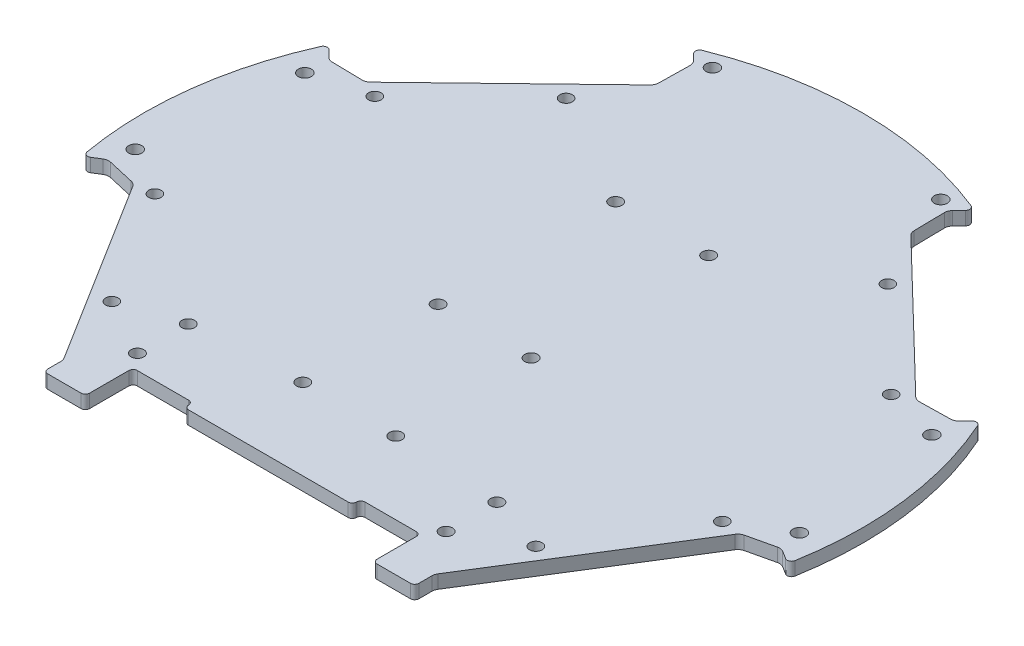
SolidWorks part; units mm, degrees
material "6061 Alloy"
ref_plane "Front Plane" through (0, 0, 0) normal (0, 0, 1) x (1, 0, 0)
ref_plane "Top Plane" through (0, 0, 0) normal (0, 1, 0) x (1, 0, 0)
ref_plane "Right Plane" through (0, 0, 0) normal (1, 0, 0) x (0, 0, -1)
sketch "Sketch1" plane through (0, 0, 0) normal (0, 1, 0) x (1, 0, 0)
  line L0 (0, 0) -> (0, -55.55) construction
  line L1 (-83.4462, -16.178) -> (-71.2857, -8.5793) construction
  line L6 (0, 0) -> (-59.046, 61.1439) construction
  line L7 (0, 0) -> (-72.0841, -45.0431) construction
  line L8 (-33.174, 78.2591) -> (-23.2129, 67.9442) construction
  line L9 (-72.0841, -45.0431) -> (-70.388, -43.9833) construction
  line L10 (-70.388, -43.9833) -> (-84.9608, -20.662) construction
  line L11 (-84.9608, -20.662) -> (-72.2401, -12.7132) construction
  line L12 (-72.2401, -12.7132) -> (-43.0945, -59.3558) construction
  line L13 (-43.0945, -59.3558) -> (-55.8152, -67.3046) construction
  line L14 (-55.8152, -67.3046) -> (-70.388, -43.9833) construction
  line L21 (-59.046, 61.1439) -> (-57.6566, 59.7052)
  line L22 (-77.4385, 40.6021) -> (-37.8748, 78.8083) construction
  line L23 (-73.9694, 32.6911) -> (-77.0537, 35.885)
  line L24 (-37.8748, 78.8083) -> (-27.4549, 68.0182) construction
  line L25 (-27.4549, 68.0182) -> (-67.0186, 29.812) construction
  line L26 (-67.0186, 29.812) -> (-77.4385, 40.6021) construction
  line L27 (-43.0945, -64.8266) -> (-34, -64.8266)
  line L33 (-86.5505, -18.1178) -> (-71.2857, -8.5793) construction
  line L34 (0, 0) -> (0, 50000) construction
  line L35 (0, 0) -> (-50000, 0) construction
  line L36 (-64.3366, -55.55) -> (-19.7189, -55.55) construction
  line L38 (-67.0927, 25.57) -> (-79.5965, 38.5181) construction
  line L39 (-54.9774, -64.8266) -> (0, -64.8266) construction
  line L40 (-35.7168, 80.8923) -> (-23.2129, 67.9442) construction
  line L41 (-38.9606, -60.3102) -> (-54.2255, -69.8488) construction
  line L42 (-34, -55.55) -> (-19.7189, -55.55) construction
  line L43 (-43.0945, -64.8266) -> (-43.0945, -58.4123) construction
  line L45 (73.9694, 32.6911) -> (77.0537, 35.885)
  line L46 (-71.2857, -8.5793) -> (-38.9606, -60.3102) construction
  line L47 (83.4462, -16.178) -> (79.6809, -13.8252)
  line L48 (69.4846, -16.1792) -> (43.8945, -57.132)
  line L50 (43.0945, -64.8266) -> (34, -64.8266)
  line L51 (34, -55.55) -> (34, -64.8266)
  line L52 (0, 0) -> (72.0841, -45.0431) construction
  line L53 (0, 0) -> (59.046, 61.1439) construction
  line L54 (-30.0897, 75.0653) -> (-30.2847, 63.8954)
  line L55 (-62.7996, 32.4961) -> (-30.2847, 63.8954)
  line L56 (-30.0897, 75.0653) -> (-33.174, 78.2591)
  line L57 (73.9694, 32.6911) -> (77.0537, 35.885)
  line L58 (30.0897, 75.0653) -> (33.174, 78.2591)
  line L59 (-34, -55.55) -> (-34, -53.55)
  line L60 (62.7996, 32.4961) -> (30.2847, 63.8954)
  line L61 (-73.9694, 32.6911) -> (-62.7996, 32.4961)
  line L62 (-77.0537, 35.885) -> (-67.0927, 25.57) construction
  line L63 (-83.4462, -16.178) -> (-79.6809, -13.8252)
  line L64 (-79.6809, -13.8252) -> (-69.4846, -16.1792)
  line L65 (-69.4846, -16.1792) -> (-43.8945, -57.132)
  line L66 (-27.4549, 68.0182) -> (-23.2129, 67.9442) construction
  line L67 (-72.2401, -12.7132) -> (-71.2857, -8.5793) construction
  line L68 (30.0897, 75.0653) -> (30.2847, 63.8954)
  line L69 (73.9694, 32.6911) -> (62.7996, 32.4961)
  line L70 (-34, -55.55) -> (-34, -64.8266)
  line L71 (79.6809, -13.8252) -> (69.4846, -16.1792)
  line L72 (-34, -53.55) -> (-20, -53.55)
  line L73 (-20, -53.55) -> (-19.7189, -55.55)
  line L74 (-19.7189, -55.55) -> (19.7189, -55.55)
  line L75 (20, -53.55) -> (19.7189, -55.55)
  line L76 (34, -53.55) -> (20, -53.55)
  line L77 (34, -55.55) -> (34, -53.55)
  line L78 (-43.0945, -64.8266) -> (-43.8945, -64.8266)
  line L79 (-19.7189, -55.55) -> (0, -55.55) construction
  line L80 (-19.7189, -55.55) -> (34, -55.55) construction
  line L81 (-43.8945, -64.8266) -> (-43.8945, -57.132)
  line L82 (-43.0945, -58.4123) -> (-43.8945, -57.132) construction
  line L83 (43.8945, -64.8266) -> (43.8945, -57.132)
  line L84 (43.0945, -64.8266) -> (43.8945, -64.8266)
  line L97 (-23.2129, 67.9442) -> (-67.0927, 25.57) construction
  circle A0 centre (0, 0) radius 85 construction
  circle A1 centre (0, 0) radius 90 construction
  arc A51 (-77.0537, 35.885) -> (-83.4462, -16.178) centre (0, 0) ccw
  arc A52 (77.0537, 35.885) -> (83.4462, -16.178) centre (0, 0) cw
  arc A54 (-33.174, 78.2591) -> (33.174, 78.2591) centre (0, 0) cw
  point P29 (-31.6318, 76.6622)
  point P33 (-47.2368, 48.9151)
  point P34 (31.6318, 76.6622)
  point P35 (-57.6673, -36.0345)
  point P85 (-57.6566, 59.7052)
  dimension "D2" = 58
  dimension "D10" = 82
  dimension "D12" = 170
  dimension "D14" = 34
  dimension "D13" = 2
  dimension "D15" = 3
  dimension "D3" = 180
  dimension "D4" = 64.8266
  dimension "D5" = 44
  dimension "D6" = 15
  dimension "D7" = 55
  dimension "D8" = 55.55
  dimension "D9" = 2
  dimension "D11" = 2
  dimension "D16" = 7
  dimension "D17" = 7
  dimension "D18" = 0.5
  dimension "D19" = 1
  dimension "D20" = 14
  dimension "D21" = 0.8
extrude "Boss-Extrude4" add sketch "Sketch1" along normal mid plane 3.175 contours A0 L70 region at (0, 0, -7.394)
ref_point "Rear_Axle_Center (L)"
ref_axis "Rear_Axle_Proj (L)" through (46.5421, 0, -48.1958) along (0, 1, 0)
ref_point "Front_Axle_Center (L)"
ref_axis "Front_Axle_Proj (L)" through (57.2432, 0, 35.7696) along (0, 1, 0)
ref_point "Front_Axle_Center (R)"
ref_axis "Front_Axle_Proj (R)" through (-57.2432, 0, 35.7696) along (0, 1, 0)
ref_point "Read_Axle_Center (R)"
ref_axis "Rear_Axle_Proj (R)" through (-46.5421, 0, -48.1958) along (0, 1, 0)
sketch "Sketch17" plane through (0, 1.5875, 0) normal (0, 1, 0) x (1, 0, 0)
  line L0 (0, -50.55) -> (0, -55.55) construction
  line L1 (-19.7189, -55.55) -> (19.7189, -55.55) construction
  circle A0 centre (0, -50.55) radius 8.5
  dimension "D1" = 17
  dimension "D2" = 5
extrude "Boss-Extrude5" [suppressed] add sketch "Sketch17" against normal up to surface (3.175 mm away)
ref_plane "Plane1" through (0, 0, 10) normal (0, 0, 1) x (1, 0, 0)
hole_wizard "M3 Clearance Hole3" positions "Sketch18" profile "Sketch19" hole size "M3" standard "ANSI Metric" end condition through all
sketch "Sketch18" plane through (0, -1.5875, 0) normal (0, -1, 0) x (-1, 0, 0)
  line L0 (-36.5, -50) -> (-36.5, -38) construction
  line L3 (0, 0) -> (0, -38) construction
  line L4 (36.5, -50) -> (36.5, -38) construction
  line L6 (0, -38) -> (36.5, -38) construction
  line L8 (0, -38) -> (-36.5, -38) construction
  line L9 (-36.5, -44) -> (36.5, -44) construction
  line L10 (0, -44) -> (0, 0) construction
  point P1 (36.5, -50)
  point P3 (36.5, -38)
  point P5 (-36.5, -50)
  point P33 (-36.5, -38)
  dimension "D1" = 12
  dimension "D2" = 73
  dimension "D4" = 38
sketch "Sketch19" plane through (-36.5, -1.5875, 50) normal (1, 0, 0) x (0, 0, -1)
  line L0 (0, 0) -> (0, 3.175)
  line L1 (0, 3.175) -> (1.5, 3.175)
  line L2 (1.5, 3.175) -> (1.5, 0)
  line L5 (1.5, 0) -> (0, 0)
  line L11 (0, -6.35) -> (0, 107.95) construction
  dimension "Thru Hole Dia." = 3
  dimension "Thru Hole Depth" = 3.175
hole_wizard "M3 Clearance Hole1" positions "Sketch11" profile "Sketch12" hole size "M3" standard "ANSI Metric" end condition through all
sketch "Sketch11" plane through (0, 1.5875, 0) normal (0, 1, 0) x (1, 0, 0)
  line L0 (83.4462, -16.178) -> (79.6809, -13.8252) construction
  line L2 (73.9694, 32.6911) -> (77.0537, 35.885) construction
  line L4 (-73.9694, 32.6911) -> (-77.0537, 35.885) construction
  line L6 (0, 0) -> (0, -50000) construction
  line L7 (78.4111, 9.6277) -> (84.3664, 10.3589) construction
  line L10 (74.155, 27.2403) -> (78.5423, -8.4914) construction
  line L12 (78.4111, 9.6277) -> (76.3487, 9.3744) construction
  arc A7 (77.964, -12.7523) -> (72.563, 31.2347) centre (0, 0) ccw construction
  arc A13 (-77.964, -12.7523) -> (-72.563, 31.2347) centre (0, 0) cw construction
  arc A17 (83.4462, -16.178) -> (77.0537, 35.885) centre (0, 0) ccw construction
  point P34 (78.5423, -8.4914)
  point P66 (74.155, 27.2403)
  point P70 (-74.155, 27.2403)
  point P71 (-78.5423, -8.4914)
  dimension "D1" = 6
  dimension "D2" = 36
sketch "Sketch12" plane through (-78.5423, 1.5875, 8.4914) normal (1, 0, 0) x (0, 0, 1)
  line L0 (0, 0) -> (0, 3.175)
  line L1 (0, 3.175) -> (1.55, 3.175)
  line L2 (1.55, 3.175) -> (1.55, 0)
  line L5 (1.55, 0) -> (0, 0)
  line L11 (0, -6.35) -> (0, 107.95) construction
  dimension "Thru Hole Dia." = 3.1
  dimension "Thru Hole Depth" = 3.175
hole_wizard "M3 Clearance Hole4" positions "Sketch9" profile "Sketch10" hole size "M3" standard "ANSI Metric" end condition through all
sketch "Sketch9" plane through (0, -1.5875, 0) normal (0, -1, 0) x (-1, 0, 0)
  line L0 (0, 0) -> (0, 63.4318) construction
  line L1 (-38.0437, 52.9272) -> (38.0437, 52.9272) construction
  line L3 (61.0625, 30.6981) -> (-61.0625, 30.6981) construction
  line L4 (-67.0993, -15.2789) -> (67.0993, -15.2789) construction
  line L5 (50.1419, -42.4164) -> (-50.1419, -42.4164) construction
  line L6 (-61.0625, 30.6981) -> (-38.0437, 52.9272) construction
  line L7 (38.0437, 52.9272) -> (61.0625, 30.6981) construction
  line L8 (67.0993, -15.2789) -> (50.1419, -42.4164) construction
  line L9 (-50.1419, -42.4164) -> (-67.0993, -15.2789) construction
  line L10 (0, 0) -> (-44.8055, 46.3974) construction
  line L11 (0, 0) -> (44.8055, 46.3974) construction
  line L12 (0, 0) -> (-96.9468, 0) construction
  line L14 (-55.1231, -34.4448) -> (0, 0) construction
  line L15 (0, 0) -> (55.1231, -34.4448) construction
  line L18 (-69.4846, -16.1792) -> (-43.8945, -57.132) construction
  line L19 (-62.7996, 32.4961) -> (-30.2847, 63.8954) construction
  point P0 (-67.0993, -15.2789)
  point P2 (-50.1419, -42.4164)
  point P9 (-61.0625, 30.6981)
  point P11 (-38.0437, 52.9272)
  point P30 (50.1419, -42.4164)
  point P31 (67.0993, -15.2789)
  point P32 (38.0437, 52.9272)
  point P33 (61.0625, 30.6981)
  dimension "D9" = 46
  dimension "D10" = 46
  dimension "D11" = 32
  dimension "D12" = 32
  dimension "D7" = 58
  dimension "D5" = 32
  dimension "D6" = 2.5
  dimension "D8" = 9.4
  dimension "D2" = 44
  dimension "D3" = 32
  dimension "D4" = 2.5
  dimension "D13" = 9.4
sketch "Sketch10" plane through (67.0993, -1.5875, 15.2789) normal (1, 0, 0) x (0, 0, -1)
  line L0 (0, 0) -> (0, 3.175)
  line L1 (0, 3.175) -> (1.475, 3.175)
  line L2 (1.475, 3.175) -> (1.475, 0)
  line L5 (1.475, 0) -> (0, 0)
  line L11 (0, -6.35) -> (0, 107.95) construction
  dimension "Thru Hole Dia." = 2.95
  dimension "Thru Hole Depth" = 3.175
hole_wizard "M3 Clearance Hole2" positions "Sketch13" profile "Sketch14" hole size "M3" standard "ANSI Metric" end condition through all
sketch "Sketch13" plane through (0, 1.5875, 0) normal (0, 1, 0) x (1, 0, 0)
  line L0 (0, 0) -> (0, 85) construction
  line L2 (-24, 47) -> (-24, 81) construction
  line L3 (-24, 47) -> (24, 47) construction
  line L4 (-24, 81) -> (24, 81) construction
  line L5 (24, 47) -> (24, 81) construction
  line L6 (-24, 47) -> (24, 81) construction
  line L7 (-24, 81) -> (24, 47) construction
  line L8 (-38.0437, 52.9272) -> (-61.0625, 30.6981) construction
  line L10 (-36.307, 51.1289) -> (-59.3259, 28.8998) construction
  line L11 (-16.3488, 39.8187) -> (-31.6313, 55.6441) construction
  line L12 (-16.3488, 39.8187) -> (-48.7191, 8.559) construction
  line L13 (-31.6313, 55.6441) -> (-64.0016, 24.3845) construction
  line L14 (-48.7191, 8.559) -> (-64.0016, 24.3845) construction
  line L15 (-16.3488, 39.8187) -> (-64.0016, 24.3845) construction
  line L16 (-31.6313, 55.6441) -> (-48.7191, 8.559) construction
  line L17 (-49.5531, 41.8127) -> (-40.1752, 32.1016) construction
  line L18 (-27, 76.4978) -> (-27, 80.5978) construction
  arc A0 (33.174, 78.2591) -> (-33.174, 78.2591) centre (0, 0) ccw construction
  circle A1 centre (-16.2162, 44) radius 3 construction
  circle A2 centre (-27, 76.4978) radius 3 construction
  point P65 (0, 64)
  point P181 (-27, 76.4978)
  point P184 (27, 76.4978)
  dimension "D7" = 6
  dimension "D1" = 48
  dimension "D2" = 34
  dimension "D3" = 4
  dimension "D5" = 45
  dimension "D6" = 22
  dimension "D8" = 4.1
  dimension "D4" = 2.5
sketch "Sketch14" plane through (27, 1.5875, -76.4978) normal (1, 0, 0) x (0, 0, 1)
  line L0 (0, 0) -> (0, 3.175)
  line L1 (0, 3.175) -> (1.55, 3.175)
  line L2 (1.55, 3.175) -> (1.55, 0)
  line L5 (1.55, 0) -> (0, 0)
  line L11 (0, -6.35) -> (0, 107.95) construction
  dimension "Thru Hole Dia." = 3.1
  dimension "Thru Hole Depth" = 3.175
hole_wizard "M3 Clearance Hole5" positions "Sketch24" profile "Sketch25" hole size "M3" standard "ANSI Metric" end condition through all
sketch "Sketch24" plane through (0, 1.5875, 0) normal (0, 1, 0) x (1, 0, 0)
  line L1 (-11, -4.4) -> (11, -4.4) construction
  line L2 (11, -4.4) -> (11, -36.4) construction
  line L3 (11, -36.4) -> (-11, -36.4) construction
  line L4 (-11, -36.4) -> (-11, -4.4) construction
  line L7 (-11, 37.6) -> (11, 37.6) construction
  line L8 (0, -4.4) -> (0, 0) construction
  line L9 (0, 0) -> (0, 37.6) construction
  point P8 (-11, -4.4)
  point P10 (11, -4.4)
  point P12 (11, -36.4)
  point P14 (-11, -36.4)
  point P42 (-11, 37.6)
  point P45 (11, 37.6)
  dimension "D1" = 22
  dimension "D2" = 32
  dimension "D3" = 4.4
  dimension "D4" = 42
sketch "Sketch25" plane through (-11, 1.5875, 4.4) normal (1, 0, 0) x (0, 0, 1)
  line L0 (0, 0) -> (0, 3.175)
  line L1 (0, 3.175) -> (1.5, 3.175)
  line L2 (1.5, 3.175) -> (1.5, 0)
  line L5 (1.5, 0) -> (0, 0)
  line L11 (0, -6.35) -> (0, 107.95) construction
  dimension "Thru Hole Dia." = 3
  dimension "Thru Hole Depth" = 3.175
sketch "Sketch20" plane through (0, 1.5875, 0) normal (0, 1, 0) x (1, 0, 0)
  line L0 (-16.1485, 44) -> (-16.1485, 39) construction
  line L1 (-14.6485, 44) -> (-14.6485, 39)
  line L2 (-17.6485, 44) -> (-17.6485, 39)
  line L3 (0, 0) -> (0, 85) construction
  line L5 (16.1485, 44) -> (16.1485, 39) construction
  line L6 (14.6485, 44) -> (14.6485, 39)
  line L7 (17.6485, 44) -> (17.6485, 39)
  arc A0 (-14.6485, 44) -> (-17.6485, 44) centre (-16.1485, 44) ccw
  arc A1 (-17.6485, 39) -> (-14.6485, 39) centre (-16.1485, 39) ccw
  arc A5 (33.174, 78.2591) -> (-33.174, 78.2591) centre (0, 0) ccw construction
  arc A7 (14.6485, 44) -> (17.6485, 44) centre (16.1485, 44) cw
  arc A8 (17.6485, 39) -> (14.6485, 39) centre (16.1485, 39) cw
  point P2 (-16.1485, 41.5)
  point P16 (16.1485, 41.5)
  dimension "D1" = 44
  dimension "D2" = 3
  dimension "D3" = 5
  dimension "D4" = 16.1485
extrude "Cut-Extrude1" [suppressed] cut sketch "Sketch20" against normal through all
sketch "Sketch22" plane through (0, 1.5875, 0) normal (0, 1, 0) x (1, 0, 0)
  line L0 (-56.6896, -36.6556) -> (-58.0464, -37.5035) construction
  line L1 (-69.4846, -16.1792) -> (-43.8945, -57.132) construction
  line L3 (30.2452, 66.1578) -> (65.062, 32.5356)
  line L4 (71.6894, -15.6702) -> (43.8945, -60.1514)
  line L5 (-19.7189, -55.55) -> (19.7189, -55.55) construction
  line L6 (-43.8945, -64.8266) -> (-43.8945, -57.132) construction
  line L28 (-30.2452, 66.1578) -> (-65.062, 32.5356)
  line L29 (-71.6894, -15.6702) -> (-43.8945, -60.1514)
  line L30 (-79.6809, -13.8252) -> (-69.4846, -16.1792) construction
  line L31 (0, 85) -> (0, -55.55) construction
  line L32 (-46.5421, 48.1958) -> (-47.6536, 49.3467) construction
  line L37 (-20, -53.55) -> (-19.7189, -55.55)
  line L38 (-20, -53.55) -> (-19.7189, -55.55)
  line L40 (-43.8945, -57.132) -> (-43.8945, -64.8266)
  line L41 (-43.8945, -57.132) -> (-43.8945, -64.8266)
  line L43 (43.8945, -64.8266) -> (43.8945, -57.132)
  line L44 (43.8945, -64.8266) -> (43.8945, -57.132)
  line L56 (-19.7189, -55.55) -> (19.7189, -55.55)
  line L58 (19.7189, -55.55) -> (20, -53.55)
  line L59 (20, -53.55) -> (34, -53.55)
  line L60 (34, -53.55) -> (34, -64.8266)
  line L61 (34, -64.8266) -> (43.8945, -64.8266)
  line L63 (43.8945, -57.132) -> (69.4846, -16.1792)
  line L64 (69.4846, -16.1792) -> (79.6809, -13.8252)
  line L65 (79.6809, -13.8252) -> (83.4462, -16.178)
  line L66 (77.0537, 35.885) -> (73.9694, 32.6911)
  line L67 (73.9694, 32.6911) -> (62.7996, 32.4961)
  line L68 (62.7996, 32.4961) -> (30.2847, 63.8954)
  line L69 (30.2847, 63.8954) -> (30.0897, 75.0653)
  line L70 (30.0897, 75.0653) -> (33.174, 78.2591)
  line L71 (-33.174, 78.2591) -> (-30.0897, 75.0653)
  line L72 (-30.0897, 75.0653) -> (-30.2847, 63.8954)
  line L73 (-30.2847, 63.8954) -> (-62.7996, 32.4961)
  line L74 (-62.7996, 32.4961) -> (-73.9694, 32.6911)
  line L75 (-73.9694, 32.6911) -> (-77.0537, 35.885)
  line L76 (-83.4462, -16.178) -> (-79.6809, -13.8252)
  line L77 (-79.6809, -13.8252) -> (-69.4846, -16.1792)
  line L78 (-69.4846, -16.1792) -> (-43.8945, -57.132)
  line L80 (-43.8945, -64.8266) -> (-34, -64.8266)
  line L81 (-34, -64.8266) -> (-34, -53.55)
  line L82 (-34, -53.55) -> (-20, -53.55)
  line L84 (-19.7189, -55.55) -> (19.7189, -55.55)
  line L86 (19.7189, -55.55) -> (20, -53.55)
  line L87 (20, -53.55) -> (34, -53.55)
  line L88 (34, -53.55) -> (34, -64.8266)
  line L89 (34, -64.8266) -> (43.8945, -64.8266)
  line L91 (43.8945, -57.132) -> (69.4846, -16.1792)
  line L92 (69.4846, -16.1792) -> (79.6809, -13.8252)
  line L93 (79.6809, -13.8252) -> (83.4462, -16.178)
  line L94 (77.0537, 35.885) -> (73.9694, 32.6911)
  line L95 (73.9694, 32.6911) -> (62.7996, 32.4961)
  line L96 (62.7996, 32.4961) -> (30.2847, 63.8954)
  line L97 (30.2847, 63.8954) -> (30.0897, 75.0653)
  line L98 (30.0897, 75.0653) -> (33.174, 78.2591)
  line L99 (-33.174, 78.2591) -> (-30.0897, 75.0653)
  line L100 (-30.0897, 75.0653) -> (-30.2847, 63.8954)
  line L101 (-30.2847, 63.8954) -> (-62.7996, 32.4961)
  line L102 (-62.7996, 32.4961) -> (-73.9694, 32.6911)
  line L103 (-73.9694, 32.6911) -> (-77.0537, 35.885)
  line L104 (-83.4462, -16.178) -> (-79.6809, -13.8252)
  line L105 (-79.6809, -13.8252) -> (-69.4846, -16.1792)
  line L106 (-69.4846, -16.1792) -> (-43.8945, -57.132)
  line L108 (-43.8945, -64.8266) -> (-34, -64.8266)
  line L109 (-34, -64.8266) -> (-34, -53.55)
  line L110 (-34, -53.55) -> (-20, -53.55)
  arc A9 (83.4462, -16.178) -> (77.0537, 35.885) centre (0, 0) ccw
  arc A10 (33.174, 78.2591) -> (-33.174, 78.2591) centre (0, 0) ccw
  arc A11 (-77.0537, 35.885) -> (-83.4462, -16.178) centre (0, 0) ccw
  arc A13 (83.4462, -16.178) -> (77.0537, 35.885) centre (0, 0) ccw
  arc A14 (33.174, 78.2591) -> (-33.174, 78.2591) centre (0, 0) ccw
  arc A15 (-77.0537, 35.885) -> (-83.4462, -16.178) centre (0, 0) ccw
  dimension "D2" = 1.6
  dimension "D1" = 0
extrude "Boss-Extrude6" add sketch "Sketch22" against normal up to surface (3.175 mm away) contours L102 L101 L100 L28 | L106 L105 L29 | L92 L91 L4 | L97 L96 L95 L3 region at (47.1042, 1.5875, -48.7778) region at (-47.1042, 1.5875, -48.7778) region at (57.2483, 1.5875, 37.2918) region at (-57.2483, 1.5875, 37.2918) up to face at (-11, -1.5875, 5.9)
fillet "Fillet1" radius 2 14 edges at (-30.0897, 0, -75.0653) (30.0897, 0, -75.0653) (-79.6809, 0, 13.8252) (79.6809, 0, 13.8252) (73.9694, 0, -32.6911) (-73.9694, 0, -32.6911) (65.062, 0, -32.5356) (30.2452, 0, -66.1578) (71.6894, 0, 15.6702) (-71.6894, 0, 15.6702) (-65.062, 0, -32.5356) (-30.2452, 0, -66.1578) (43.8945, 0, 60.1514) (-43.8945, 0, 60.1514)
fillet "Fillet3" radius 1 16 edges at (-77.0537, 0, -35.885) (77.0537, 0, -35.885) (83.4462, 0, 16.178) (34, 0, 64.8266) (-34, 0, 64.8266) (-33.174, 0, -78.2591) (33.174, 0, -78.2591) (-83.4462, 0, 16.178) (20, 0, 53.55) (34, 0, 53.55) (-34, 0, 53.55) (-20, 0, 53.55) (19.7189, 0, 55.55) (-19.7189, 0, 55.55) (-43.8945, 0, 64.8266) (43.8945, 0, 64.8266)
sketch "Sketch23" [suppressed] plane through (0, 3.175, 0) normal (0, 1, 0) x (1, 0, 0)
  circle A0 centre (0, -53.55) radius 4.95
  dimension "D1" = 9.9
extrude "Cut-Extrude2" [suppressed] cut sketch "Sketch23" against normal through all
sketch "Sketch26" [suppressed] plane through (0, 3.175, 0) normal (0, 1, 0) x (1, 0, 0)
  line L0 (0, 0) -> (0, 50) construction
  line L1 (-92.5, 5) -> (92.5, 5)
  line L2 (-92.5, 5) -> (-92.5, 95)
  line L3 (-92.5, 95) -> (92.5, 95)
  line L4 (92.5, 5) -> (92.5, 95)
  line L5 (-92.5, 5) -> (92.5, 95) construction
  line L6 (-92.5, 95) -> (92.5, 5) construction
  point P0 (0, 50)
  dimension "D1" = 90
  dimension "D2" = 185
  dimension "D3" = 5
extrude "Cut-Extrude3" [suppressed] cut sketch "Sketch26" against normal through all
fillet "Fillet4" [suppressed] radius 5
equation "\"D3@Sketch9\"=\"D5@Sketch9\""
equation "\"D4@Sketch9\"=\"D6@Sketch9\""
equation "\"D13@Sketch9\"=\"D8@Sketch9\""
